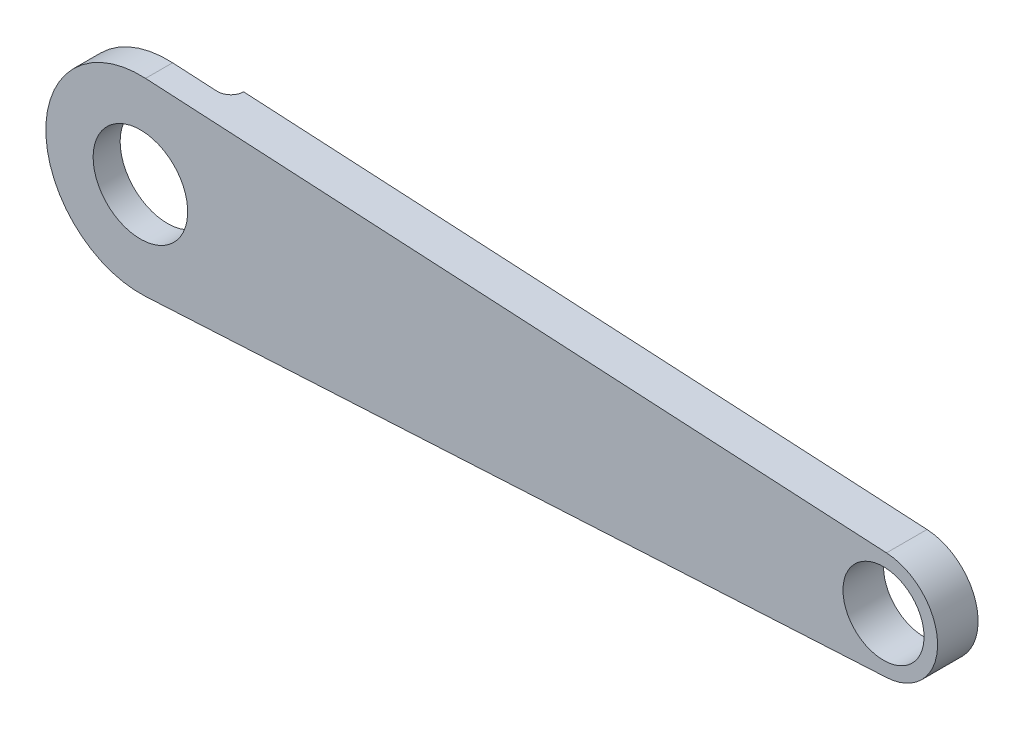
SolidWorks part; units mm, degrees
ref_plane "Front Plane" through (0, 0, 0) normal (0, 0, 1) x (1, 0, 0)
ref_plane "Top Plane" through (0, 0, 0) normal (0, 1, 0) x (1, 0, 0)
ref_plane "Right Plane" through (0, 0, 0) normal (1, 0, 0) x (0, 0, -1)
sketch "Sketch1" plane through (0, 0, 0) normal (0, 0, 1) x (1, 0, 0)
  line L0 (-698.5, 0) -> (-609.6, 0) construction
  line L1 (-688.8018, 177.5353) -> (704.0418, 101.4487)
  line L2 (-688.8018, -177.5353) -> (704.0418, -101.4487)
  line L3 (-520.7, 0) -> (698.5, 0) construction
  arc A0 (-688.8018, 177.5353) -> (-688.8018, -177.5353) centre (-698.5, 0) ccw
  arc A1 (704.0418, -101.4487) -> (704.0418, 101.4487) centre (698.5, 0) ccw
  circle A2 centre (-698.5, 0) radius 88.9
  circle A3 centre (698.5, 0) radius 76.2
  point P4 (0, 0)
  dimension "D2" = 355.6
  dimension "D3" = 177.8
  dimension "D4" = 152.4
  dimension "D5" = 203.2
  dimension "D1" = 1397
extrude "Boss-Extrude1" add sketch "Sketch1" along normal mid plane 76.2
sketch "Sketch2" plane through (7.62, -139.492, 0) normal (0.0545, -0.9985, 0) x (0.9985, 0.0545, 0)
  line L0 (-875.2601, -38.1) -> (-678.0926, -38.1) construction
  line L1 (-875.2601, -38.1) -> (-570.4601, -38.1)
  line L2 (-875.2601, -38.1) -> (-875.2601, -12.7)
  line L3 (-875.2601, -12.7) -> (-570.4601, -12.7)
  line L4 (-570.4601, -38.1) -> (-570.4601, -12.7)
  dimension "D1" = 304.8
  dimension "D2" = 25.4
extrude "Cut-Extrude1" cut sketch "Sketch2" against normal through all both and the other way through all
fillet "Fillet1" radius 25.4 1 edges at (-571.3385, 0.5106, -12.7)
